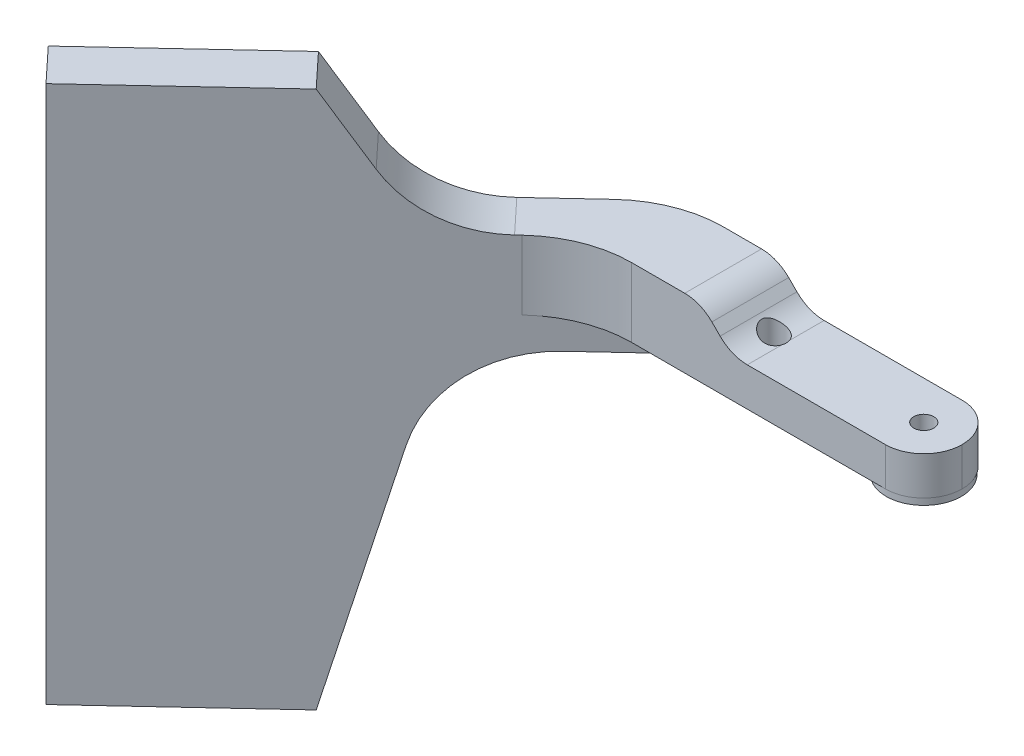
SolidWorks part; units mm, degrees
ref_plane "Front" through (0, 0, 0) normal (0, 0, 1) x (1, 0, 0)
ref_plane "Top" through (0, 0, 0) normal (0, 1, 0) x (1, 0, 0)
ref_plane "Right" through (0, 0, 0) normal (1, 0, 0) x (0, 0, -1)
sketch "Sketch1" plane through (0, 0, 0) normal (0, 1, 0) x (1, 0, 0)
  line L0 (0, 10) -> (0, 0)
  line L1 (0, 0) -> (42, 0)
  line L3 (0, 10) -> (42, 10)
  line L4 (42, 0) -> (42, 10)
  line L9 (0, 10) -> (-42.4185, -29.5559)
  line L10 (-42.4185, -29.5559) -> (-38.3265, -33.944)
  line L11 (0, 10) -> (4.092, 5.6119)
  line L12 (-38.3265, -33.944) -> (4.092, 5.6119)
  line L13 (0, 0) -> (-1.926, 0)
  line L14 (-1.926, 0) -> (0, 1.796)
  line L15 (0, 1.796) -> (0, 0)
  dimension "D1" = 10
  dimension "D2" = 42
  dimension "D3" = 223
  dimension "D4" = 58
  dimension "D5" = 6
  dimension "D6" = 270
extrude "Boss-Extrude1" add sketch "Sketch1" along normal blind 5 contours L10 L12 L1 L0 L9 | L1 L12 L11 L0 | L12 L1 L4 L3 L11 | L13 L0 L12 region at (1.364, 0, -5.8026) region at (-20.2035, 0, 12.8728) region at (21.8174, 0, -4.9666) region at (-0.642, 0, -0.5987)
fillet "Fillet1" radius 5 2 edges at (42, 2.5, 0) (42, 2.5, -10)
sketch "Sketch2" plane through (0, 5, 0) normal (0, 1, 0) x (1, 0, 0)
  circle A0 centre (37, 5) radius 1.3
extrude "Cut-Extrude1" cut sketch "Sketch2" against normal blind 10
sketch "Sketch3" plane through (0, 5, 0) normal (0, 1, 0) x (1, 0, 0)
  line L0 (-42.4185, -29.5559) -> (-38.3265, -33.944)
  line L1 (-38.3265, -33.944) -> (-20.1263, -16.972)
  line L2 (-38.3265, -33.944) -> (-1.926, 0) construction
  line L3 (-20.1263, -16.972) -> (-24.2183, -12.5839)
  line L4 (0, 10) -> (-42.4185, -29.5559) construction
  line L5 (-24.2183, -12.5839) -> (-42.4185, -29.5559)
extrude "Boss-Extrude2" add sketch "Sketch3" along normal blind 20
sketch "Sketch4" plane through (0, 0, 0) normal (0, -1, 0) x (1, 0, 0)
  line L0 (-42.4185, 29.5559) -> (-38.3265, 33.944)
  line L1 (-38.3265, 33.944) -> (-20.1263, 16.972)
  line L2 (-38.3265, 33.944) -> (-1.926, 0) construction
  line L3 (-20.1263, 16.972) -> (-24.2183, 12.5839)
  line L4 (0, -10) -> (-42.4185, 29.5559) construction
  line L5 (-24.2183, 12.5839) -> (-42.4185, 29.5559)
extrude "Boss-Extrude3" add sketch "Sketch4" along normal blind 45
sketch "Sketch5" plane through (-4.9878, 0, -5.3488) normal (-0.682, 0, -0.7314) x (-0.7314, 0, 0.682)
  line L0 (26.2943, -45) -> (26.2943, 0)
  line L1 (26.2943, 0) -> (13.889, 0)
  line L2 (-6.82, 0) -> (26.2943, 0) construction
  line L3 (13.889, 0) -> (26.2943, -45)
  line L4 (13.889, 5) -> (26.2943, 25)
  line L5 (-6.82, 5) -> (26.2943, 5) construction
  line L6 (26.2943, 25) -> (26.2943, 5)
  line L7 (26.2943, 5) -> (13.889, 5)
extrude "Boss-Extrude4" add sketch "Sketch5" against normal blind 6
sketch "Sketch6" plane through (0, 0, 0) normal (0, -1, 0) x (1, 0, 0)
  circle A0 centre (37, -5) radius 4.9
  circle A1 centre (37, -5) radius 1.3
extrude "Boss-Extrude5" add sketch "Sketch6" along normal blind 0.9
sketch "Sketch8" plane through (0, 0, 0) normal (0, -1, 0) x (1, 0, 0)
  line L0 (0, -10) -> (-19.6819, 8.3537)
  line L1 (-24.2183, 12.5839) -> (-15.1456, 4.1235) construction
  line L6 (-19.6819, 8.3537) -> (-15.5899, 12.7418)
  line L7 (-20.1263, 16.972) -> (-11.0536, 8.5116) construction
  line L8 (-15.5899, 12.7418) -> (8.7977, -10)
  line L9 (0, -10) -> (37, -10) construction
  line L10 (8.7977, -10) -> (0, -10)
extrude "Boss-Extrude6" add sketch "Sketch8" along normal blind 4
sketch "Sketch9" plane through (0, 5, 0) normal (0, 1, 0) x (1, 0, 0)
  line L3 (-15.952, -4.8755) -> (-24.2183, -12.5839) construction
  line L4 (-20.0851, -8.7297) -> (0, 10)
  line L6 (-20.0851, -8.7297) -> (-16.7996, -13.8699)
  line L7 (-20.1263, -16.972) -> (-11.0536, -8.5116) construction
  line L9 (-16.7996, -13.8699) -> (8.7977, 10)
  line L10 (0, 10) -> (37, 10) construction
  line L11 (8.7977, 10) -> (0, 10)
  line L12 (37, 0) -> (-1.926, 0) construction
  line L13 (8.7977, 0) -> (-1.926, 0)
  line L14 (-1.926, 0) -> (8.7977, 10)
  line L15 (8.7977, 10) -> (17.9505, 10)
  line L16 (17.9505, 10) -> (17.9505, 0)
  line L17 (17.9505, 0) -> (8.7977, 0)
  line M1 (-15.1456, -4.1235) -> (-11.0536, -8.5116)
  line M2 (-11.0536, -8.5116) -> (-1.926, 0)
  line M3 (-1.926, 0) -> (37, 0)
  line M6 (37, 10) -> (0, 10)
  line M7 (0, 10) -> (-15.1456, -4.1235)
extrude "Boss-Extrude7" add sketch "Sketch9" along normal blind 4 contours L9 M3 | L9 M2 M6 M7 M1 | L6 L9 L4 M1 region at (-15.7246, 5, 8.8686) region at (-4.2059, 5, -1.7921) region at (10.3631, 5, -4.3843)
fillet "Fillet2" radius 15 4 edges at (-13.906, -4, 7.0696) (-14.9141, 9, 8.0096) (-1.926, 4.5, 0) (0, 2.5, -10)
fillet "Fillet7" radius 5 1 edges at (17.9505, 9, -5) profile chamfer
fillet "Fillet8" radius 5 2 edges at (12.9505, 9, -5) (16.9505, 5, -5)
sketch "Sketch11" plane through (0, 0, 0) normal (0, -1, 0) x (-1, 0, 0)
  circle A0 centre (-17.5, 5) radius 1.6
extrude "Cut-Extrude2" cut sketch "Sketch11" against normal blind 10
